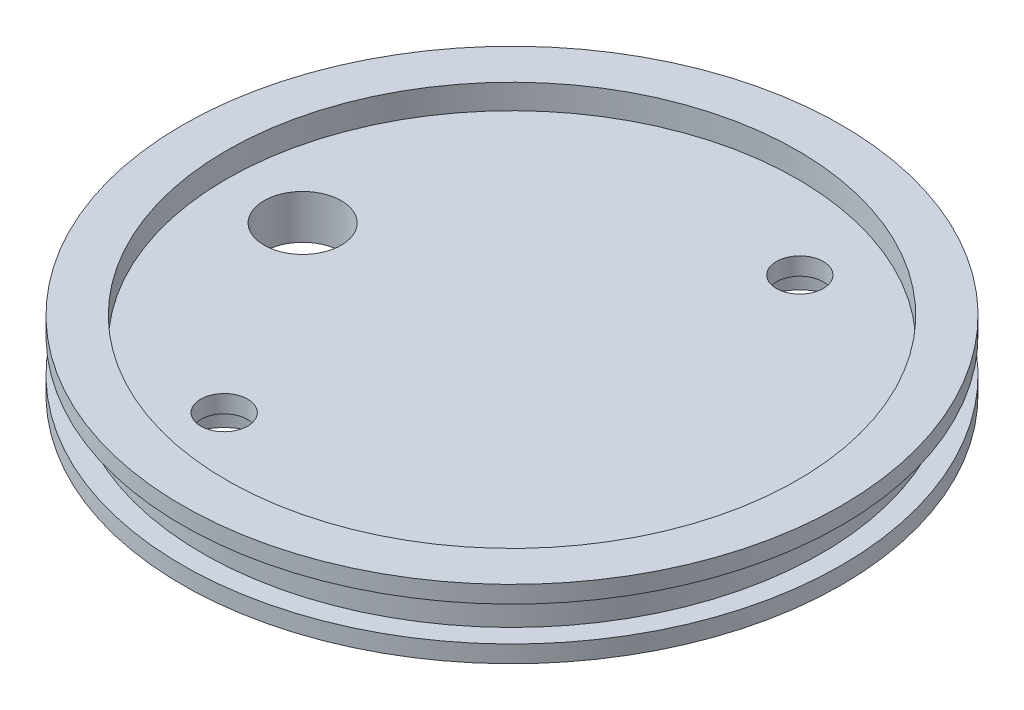
SolidWorks part; units mm, degrees
material "6061-T6 (SS)"
ref_plane "Front Plane" through (0, 0, 0) normal (0, 0, 1) x (1, 0, 0)
ref_plane "Top Plane" through (0, 0, 0) normal (0, 1, 0) x (1, 0, 0)
ref_plane "Right Plane" through (0, 0, 0) normal (1, 0, 0) x (0, 0, -1)
sketch "Sketch1" plane through (0, 0, 0) normal (0, 0, 1) x (1, 0, 0)
  line L0 (0, 48.1922) -> (0, -25.6743) construction
  line L1 (0, 0) -> (47.498, 0)
  line L2 (47.498, 0) -> (47.498, 2.4638)
  line L3 (47.498, 2.4638) -> (44.577, 2.4638)
  line L4 (44.577, 2.4638) -> (44.577, 7.4422)
  line L5 (44.577, 7.4422) -> (47.498, 7.4422)
  line L6 (47.498, 7.4422) -> (47.498, 9.906)
  line L7 (47.498, 9.906) -> (41.148, 9.906)
  line L8 (41.148, 9.906) -> (41.148, 6.35)
  line L9 (41.148, 6.35) -> (0, 6.35)
  line L10 (0, 6.35) -> (0, 0)
  dimension "D1" = 94.996
  dimension "D2" = 4.9784
  dimension "D3" = 2.921
  dimension "D4" = 9.906
  dimension "D5" = 6.35
  dimension "D6" = 6.35
revolve "Revolve1" add sketch "Sketch1" angle 360 about L0
hole_wizard "Pipe Tap Drill for 1/4 Tap1" positions "Sketch2" profile "Sketch3" hole size "1/4" standard "ANSI Inch" end condition through all
sketch "Sketch2" plane through (0, 6.35, 0) normal (0, 1, 0) x (1, 0, 0)
  point P0 (0, 0)
  point P3 (-30.1752, 0)
  dimension "D1" = 30.1752
sketch "Sketch3" plane through (0, 6.35, 0) normal (1, 0, 0) x (0, 0, 1)
  line L0 (0, 0) -> (0, 6.35)
  line L1 (0, 6.35) -> (5.5626, 6.35)
  line L2 (5.5626, 6.35) -> (5.5626, 0)
  line L5 (5.5626, 0) -> (0, 0)
  line L11 (0, -6.35) -> (0, 107.95) construction
  dimension "Thru Hole Dia." = 11.1252
  dimension "Thru Hole Depth" = 6.35
hole_wizard "CBORE for 1/4 Binding Head Machine Screw1" positions "Sketch4" profile "Sketch5" counterbore size "1/4" standard "ANSI Inch" end condition through all
sketch "Sketch4" plane through (0, 0, 0) normal (0, 1, 0) x (1, 0, 0)
  line L0 (0, 0) -> (-30.1752, 0)
  line L2 (0, 0) -> (12.1502, 29.3332)
  line L4 (0, 0) -> (-12.1502, -29.3332)
  point P0 (12.1502, 29.3332)
  point P2 (-12.1502, -29.3332)
  dimension "D1" = 31.75
  dimension "D2" = 112.5
sketch "Sketch5" plane through (12.1502, 0, -29.3332) normal (1, 0, 0) x (0, 0, -1)
  line L0 (0, 0) -> (0, 9.906)
  line L1 (0, 9.906) -> (3.3782, 9.906)
  line L3 (3.3782, 9.906) -> (3.3782, 3.81)
  line L4 (3.3782, 3.81) -> (6.35, 3.81)
  line L5 (6.35, 3.81) -> (6.35, 0)
  line L7 (6.35, 0) -> (0, 0)
  line L11 (0, -6.35) -> (0, 107.95) construction
  dimension "Thru Hole Dia." = 6.7564
  dimension "Thru Hole Depth" = 9.906
  dimension "C'Bore Dia." = 12.7
  dimension "C'Bore Depth" = 3.81
sketch "Sketch7" plane through (0, 6.35, 0) normal (0, 1, 0) x (1, 0, 0)
  circle A0 centre (0, 0) radius 11.1125
  dimension "D1" = 22.225
extrude "Boss-Extrude1" add sketch "Sketch7" against normal blind 6.35 contours A0
